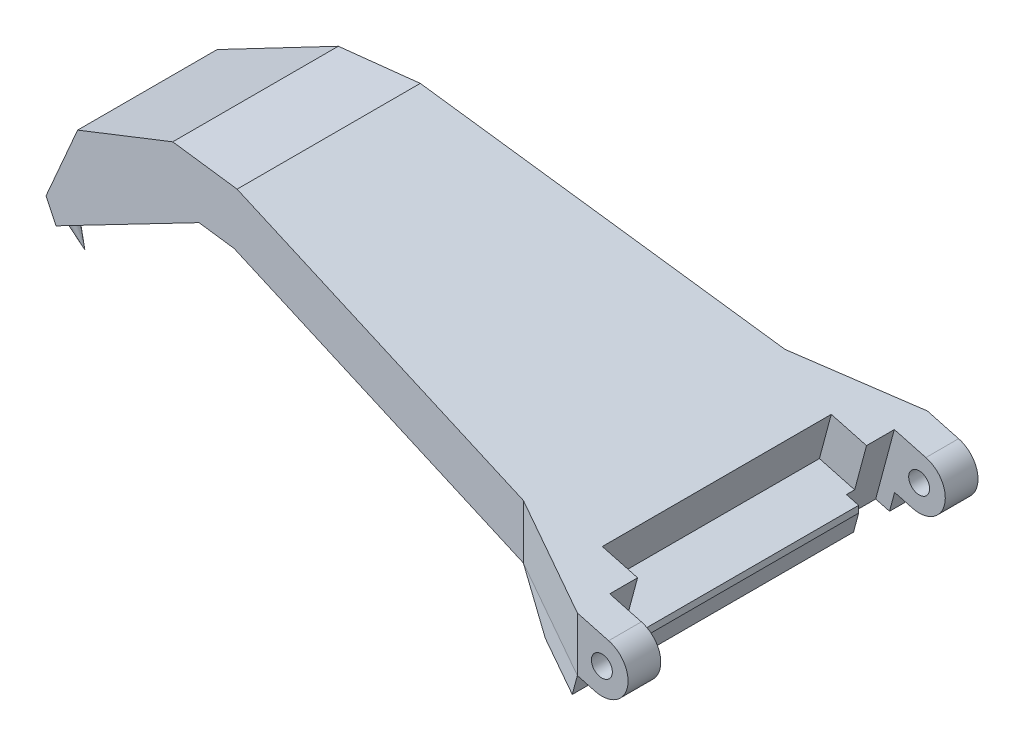
SolidWorks part; units mm, degrees
material "ABS"
ref_plane "Front Plane" through (0, 0, 0) normal (0, 0, 1) x (1, 0, 0)
ref_plane "Top Plane" through (0, 0, 0) normal (0, 1, 0) x (1, 0, 0)
ref_plane "Right Plane" through (0, 0, 0) normal (1, 0, 0) x (0, 0, -1)
sketch "Sketch3" plane through (0, 0, 0) normal (0, 0, 1) x (1, 0, 0)
  line L0 (1.0353, 3.8637) -> (-68.5163, 22.5)
  line L1 (-68.5163, 22.5) -> (-79.7011, 22.5)
  line L2 (-79.7011, 22.5) -> (-96.234, 14.7906)
  line L3 (-96.234, 14.7906) -> (-101.7321, 3)
  line L4 (-101.7321, 3) -> (-100, 0)
  line L5 (-100, 0) -> (-75.1332, 14.3568)
  line L6 (-75.1332, 14.3568) -> (-69.0353, 14.3568)
  line L7 (-69.0353, 14.3568) -> (-1.0353, -3.8637)
  line L8 (-1.0353, -3.8637) -> (1.0353, 3.8637) construction
  line L9 (-4.5341, -2.9262) -> (-2.4635, 4.8012) construction
  line L10 (-100, 0) -> (0, 0) construction
  circle A0 centre (0, 0) radius 1.6
  arc A2 (-1.0353, -3.8637) -> (1.0353, 3.8637) centre (0, 0) ccw
  point P7 (0, 0)
  point P14 (-3.75, 0)
  dimension "D2" = 3.2
  dimension "D1" = 100
  dimension "D3" = 8
  dimension "D4" = 68
  dimension "D5" = 30
  dimension "D6" = 15
  dimension "D7" = 125
  dimension "D8" = 5.498
  dimension "D9" = 3
  dimension "D10" = 155
  dimension "D11" = 22.5
sketch "start-width" plane through (0, 0, 0) normal (1, 0, 0) x (0, 0, -1)
  line L0 (-26.75, 0) -> (26.75, 0)
  point P4 (0, 0)
  dimension "D1" = 53.5
ref_plane "Plane1" through (-101.7321, 0, 0) normal (1, 0, 0) x (0, 0, -1)
sketch "end-width" plane through (-101.7321, 0, 0) normal (1, 0, 0) x (0, 0, -1)
  line L0 (10, 0) -> (-10, 0)
  point P4 (0, 0)
  dimension "D1" = 20
sketch "picture-background" plane through (0, 0, 0) normal (0, 0, 1) x (1, 0, 0)
  line L0 (-153.9208, -162.5929) -> (-22.7793, -162.5929) construction
extrude "Boss-Extrude2" add sketch "Sketch3" along direction (0, 0, -1) on the side against the normal up to vertex (26.75 mm away) and the other way up to vertex (26.75 mm away) up to point (0, 0, -26.75) other way up to point (0, 0, 26.75)
sketch "Sketch12" plane through (0, 0, 0) normal (0, 1, 0) x (1, 0, 0)
  line L0 (-101.7321, 10) -> (-101.7321, -10) construction
  line L1 (-101.7321, 10) -> (-3.75, 10) construction
  line L2 (-101.7321, 10) -> (-101.7321, -10)
  line L3 (-3.75, -26.75) -> (-3.75, 26.75)
  line L4 (-101.7321, 10) -> (-3.75, 26.75) construction
  line L5 (-101.7321, -10) -> (-3.75, -26.75) construction
  line L6 (-101.7321, 0) -> (0, 0) construction
  line L7 (0, -26.75) -> (0, 26.75) construction
  line L8 (0, -26.75) -> (0, 26.75) construction
  line L9 (-101.7321, 10) -> (-18.75, 20)
  line L10 (-18.75, 20) -> (-3.75, 26.75)
  line L11 (-18.75, -20) -> (-3.75, -26.75)
  line L12 (-101.7321, -10) -> (-18.75, -20)
  dimension "D1" = 3.75
  dimension "D2" = 20
  dimension "D3" = 15
extrude "top-form" cut sketch "Sketch12" along normal through all and the other way through all flip side to cut contours L2 L12 L11 L3 L10 L9 | L3 L10 L9 L2 L12 L11 region at (-45.7976, 0, 0)
sketch "Sketch13" plane through (0, 0, 0) normal (0, 0, 1) x (1, 0, 0)
  line L0 (-3.75, 5.1459) -> (-3.75, -3.1363) construction
  line L1 (-3.75, 5.1459) -> (-3.75, -3.1363)
  line L8 (1.0353, 3.8637) -> (-3.75, 5.1459)
  line L9 (-1.0353, -3.8637) -> (-3.75, -3.1363)
  arc A0 (-1.0353, -3.8637) -> (1.0353, 3.8637) centre (0, 0) ccw construction
  circle A1 centre (0, 0) radius 1.6 construction
  arc A2 (-1.0353, -3.8637) -> (1.0353, 3.8637) centre (0, 0) ccw
  circle A3 centre (0, 0) radius 1.6
extrude "end-extrude" add sketch "Sketch13" along direction (0, 0, 1) on the side of the normal up to vertex (26.75 mm away) and the other way up to vertex (26.75 mm away) up to point (-3.75, 5.1459, 26.75) other way up to point (-3.75, 5.1459, -26.75)
sketch "Sketch16" plane through (1.0353, 3.8637, 0) normal (0.2588, 0.9659, 0) x (0.9659, -0.2588, 0)
  line L0 (4, -26.75) -> (4, 26.75) construction
  line L1 (4, -26.75) -> (4, 26.75) construction
  line L2 (4, 26.75) -> (0, 26.75) construction
  line L3 (0, -26.75) -> (4, -26.75) construction
  line L4 (4, 26.75) -> (0, 26.75) construction
  line L5 (0, -26.75) -> (4, -26.75) construction
  line L6 (0, 26.75) -> (-4.9541, 26.75) construction
  line L7 (0, -26.75) -> (-4.9541, -26.75) construction
  line L8 (0, 26.75) -> (-4.9541, 26.75) construction
  line L9 (0, -26.75) -> (-4.9541, -26.75) construction
  line L10 (-4.9541, -26.75) -> (-4.9541, 26.75) construction
  line L11 (4, 0) -> (-4.9541, 0) construction
  line L14 (-4.9541, -21.75) -> (4, -21.75)
  line L15 (-4.9541, 21.75) -> (4, 21.75)
  line L16 (4, -21.75) -> (-4.9541, -21.75)
  line L17 (-4.9541, -21.75) -> (-4.9541, 0)
  line L18 (4, 0) -> (4, -21.75)
  line L19 (-4.9541, 21.75) -> (-4.9541, 0)
  line L20 (4, 0) -> (4, 21.75)
  line L21 (4, 0) -> (4, -21.75)
  line L22 (-4.9541, -21.75) -> (-4.9541, 0)
  line M12 (0, -26.75) -> (0, 26.75)
  dimension "D1" = 43.5
extrude "spring_phalanx_place" cut sketch "Sketch16" along direction (0, -1, 0) on the side against the normal up to surface (8 mm away) contours L15 L19 L17 L14 M12 | L18 L20 L15 L14 M12 region at (-1.3574, 4.5048, 0) region at (2.9671, 3.3461, 0) up to face at (-23.1426, 2.0599, 0)
sketch "Sketch17" plane through (-25, 43.3013, 0) normal (0.5, -0.866, 0) x (0.866, 0.5, 0)
  line L0 (-86.6025, 0) -> (-57.8889, 0) construction
  line L1 (-86.6025, -10.2087) -> (-86.6025, 10.2087) construction
  line L2 (-57.8889, -13.2054) -> (-57.8889, 13.2054) construction
  line L3 (-86.6025, 10.2087) -> (-57.8889, 13.2054) construction
  circle A0 centre (-85.1025, 8.8571) radius 0.75
  circle A1 centre (-85.1025, -8.8571) radius 0.75
  dimension "D1" = 1.5
  dimension "D2" = 1.5
  dimension "D3" = 1.5
extrude "spikes" add sketch "Sketch17" along normal blind 6 draft 12
sketch "Sketch18" plane through (-1.0353, -3.8637, 0) normal (-0.2588, -0.9659, 0) x (0.9659, -0.2588, 0)
  line L0 (-18.3396, -20) -> (-2.8105, -26.75) construction
  line L2 (-18.3396, 20) -> (-2.8105, 26.75) construction
  line L4 (-2.8105, 26.75) -> (-2.8105, -26.75)
  line L5 (-18.3396, -20) -> (-18.3396, 20)
  line L7 (-18.3396, 20) -> (-2.8105, 26.75)
  line L8 (-18.3396, -20) -> (-2.8105, -26.75)
  line L9 (-2.8105, 26.75) -> (0, 26.75) construction
  line L10 (0, 26.75) -> (0, -26.75) construction
  line L11 (0, -26.75) -> (-2.8105, -26.75)
  line M4 (-2.8105, 26.75) -> (-18.3396, 20)
  line M8 (-18.3396, -20) -> (-2.8105, -26.75)
  line M12 (-2.8105, -21.75) -> (-2.8105, 21.75)
extrude "spring-support" add sketch "Sketch18" along normal blind 3 contours L5 L4 M8 M12 M4 region at (-10.889, -1.2234, 0)
ref_plane "spring-cut-out-plane" through (-0.7765, -2.8978, 0) normal (0.2588, 0.9659, 0) x (0.9659, -0.2588, 0)
sketch "Sketch21" plane through (-0.7765, -2.8978, 0) normal (0.2588, 0.9659, 0) x (0.9659, -0.2588, 0)
  line L0 (-4.9541, 21.75) -> (0, 21.75) construction
  line L1 (-4.9541, 21.75) -> (0, 21.75)
  line L2 (0, 0) -> (-11, 0) construction
  line L3 (-4.9541, -21.75) -> (0, -21.75) construction
  line L4 (-4.9541, -21.75) -> (-5, -21.75)
  line L5 (-4.9541, -21.75) -> (0, -21.75)
  line L6 (0, 16.25) -> (-5, 16.25)
  line L8 (-5, -21.75) -> (-5, -16.25)
  line L12 (0, -16.25) -> (0, -21.75)
  line L13 (0, 16.25) -> (0, 21.75)
  line L16 (-4.9541, 21.75) -> (-5, 21.75)
  line L17 (-5, 21.75) -> (-5, 16.25)
  line L19 (0, -16.25) -> (-5, -16.25)
  dimension "D1" = 5.5
  dimension "D3" = 5
sketch "Sketch22" plane through (0, 0, 0) normal (0, 0, 1) x (1, 0, 0)
  line L0 (-19.5265, -2.0148) -> (-18.75, 0.8829) construction
  line L1 (-19.5265, -2.0148) -> (-18.75, 0.8829)
  line L2 (-3.75, 5.1459) -> (-3.75, -3.1363) construction
  line L3 (-19.5265, -2.0148) -> (-4.5265, -6.0341) construction
  line L4 (-18.75, 0.8829) -> (-12.0265, -4.0245)
  line L5 (-12.0265, -4.0245) -> (-19.5265, -2.0148)
  line L6 (-19.5265, -2.0148) -> (-4.5265, -6.0341) construction
  line L7 (-18.75, 0.8829) -> (-3.75, -3.1363) construction
  line L8 (-3.75, -2.101) -> (-10.9944, -0.1599)
  line L9 (-10.9944, -0.1599) -> (-8.4063, 9.4994)
  line L12 (-3.75, 5.1459) -> (-3.75, -3.1363) construction
  line L13 (-3.75, 8.2517) -> (-3.75, -2.101)
  line L14 (-18.75, 0.8829) -> (-3.75, -3.1363) construction
  line L15 (-3.75, 8.2517) -> (-3.75, -3.1363) construction
  line L16 (-8.4063, 9.4994) -> (-3.75, 8.2517)
  dimension "D1" = 7.5
  dimension "D2" = 1
  dimension "D3" = 10
extrude "spring-support-corner-cut" cut sketch "Sketch22" against normal through all both and the other way through all contours L4 L5 L1
extrude "spring-place-cut" cut sketch "Sketch22<3>" along normal blind 17.5 and the other way blind 17.5 contours L13 L8 L9 L16
sketch "Sketch22<3>" plane through (0, 0, 0) normal (0, 0, 1) x (1, 0, 0) same geometry as "Sketch22"
extrude "phalanx-space-cut" cut sketch "Sketch21" against normal through all both and the other way through all
